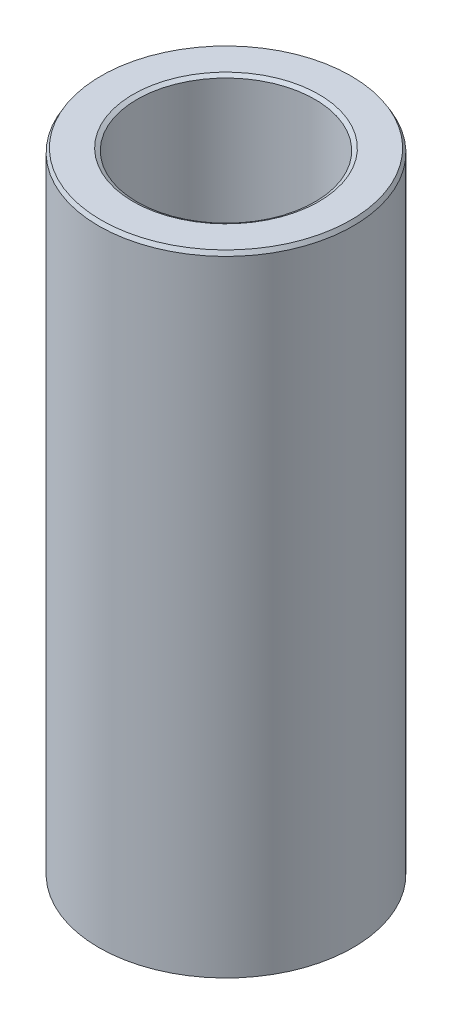
SolidWorks part; units mm, degrees
ref_plane "Front Plane" through (0, 0, 0) normal (0, 0, 1) x (1, 0, 0)
ref_plane "Top Plane" through (0, 0, 0) normal (0, 1, 0) x (1, 0, 0)
ref_plane "Right Plane" through (0, 0, 0) normal (1, 0, 0) x (0, 0, -1)
sketch "Sketch1" plane through (0, 0, 0) normal (0, 1, 0) x (1, 0, 0)
  circle A0 centre (0, 0) radius 17.5
  dimension "SLEEVE_OD" = 35
extrude "Boss-Extrude1" add sketch "Sketch1" along normal blind 86.8304
sketch "Sketch2" plane through (0, 0, 0) normal (0, 1, 0) x (1, 0, 0)
  circle A0 centre (0, 0) radius 12.232
  dimension "BORE_D" = 24.464
extrude "Cut-Extrude1" cut sketch "Sketch2" along normal through all
chamfer "Chamfer1" distance 0.5493 angle 30 4 edges at (0, 86.8304, 12.232) (0, 0, 12.232) (0, 0, 17.5) (0, 86.8304, 17.5) first distance on face at (0, 86.8304, 12.232) first distance on face at (0, 0, 12.232) first distance on face at (0, 86.8304, 17.5)
